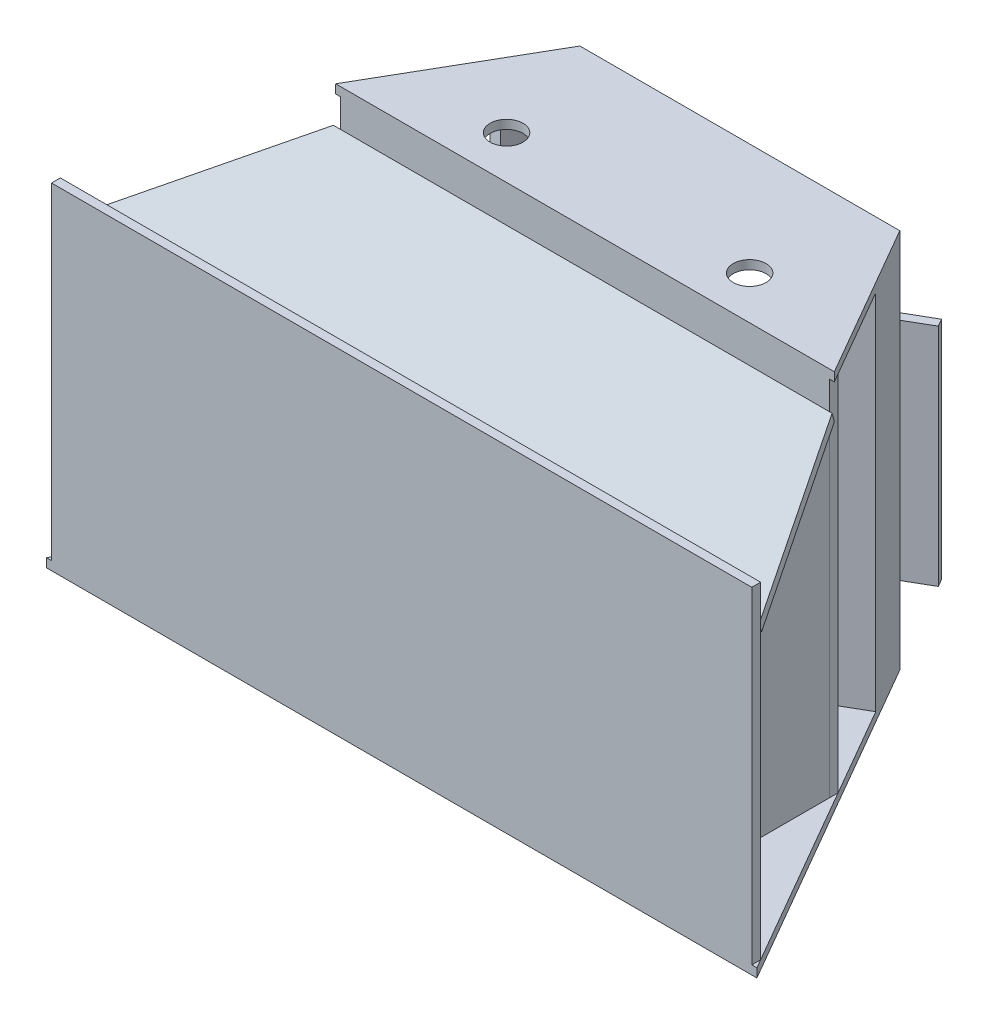
SolidWorks part; units mm, degrees
material "Pine"
ref_plane "Front Plane" through (0, 0, 0) normal (0, 0, 1) x (1, 0, 0)
ref_plane "Top Plane" through (0, 0, 0) normal (0, 1, 0) x (1, 0, 0)
ref_plane "Right Plane" through (0, 0, 0) normal (1, 0, 0) x (0, 0, -1)
sketch "TOP LAYOUT" plane through (0, 0, 0) normal (0, 1, 0) x (1, 0, 0)
  line L0 (-480.2035, -831.7368) -> (0, 0) construction
  line L1 (960.407, 0) -> (480.2035, 831.7368)
  line L2 (480.2035, 831.7368) -> (-480.2035, 831.7368)
  line L3 (-480.2035, 831.7368) -> (-960.407, 0)
  line L4 (-960.407, 0) -> (-480.2035, -831.7368)
  line L5 (-480.2035, -831.7368) -> (480.2035, -831.7368)
  line L6 (480.2035, -831.7368) -> (960.407, 0)
  line L7 (0, 0) -> (480.2035, -831.7368) construction
  circle A0 centre (0, 0) radius 831.7368 construction
  dimension "D1" = 1663.4737
sketch "REEF" plane through (0, 0, 0) normal (1, 0, 0) x (0, 0, -1)
  line L0 (-831.7368, 0) -> (-831.7368, 454.025)
  line L1 (-831.7368, 454.025) -> (-819.8306, 454.025)
  line L2 (-819.8306, 454.025) -> (-819.8306, 404.9259)
  line L3 (-819.8306, 404.9259) -> (-583.9002, 468.1433)
  line L4 (-583.9002, 468.1433) -> (-583.9002, 514.3505)
  line L5 (-583.9002, 514.3505) -> (-547.8322, 514.3505)
  line L6 (-547.8322, 514.3505) -> (-547.8322, 601.9982)
  line L7 (-547.8322, 601.9982) -> (-791.3462, 772.5085)
  line L8 (-791.3462, 772.5085) -> (-767.162, 807.0473)
  line L9 (-767.162, 807.0473) -> (-547.8322, 653.4709)
  line L10 (-547.8322, 653.4709) -> (-547.8322, 1005.0979)
  line L11 (-547.8322, 1005.0979) -> (-791.3462, 1175.6083)
  line L12 (-791.3462, 1175.6083) -> (-767.162, 1210.147)
  line L13 (-767.162, 1210.147) -> (-547.8322, 1056.5707)
  line L14 (-547.8322, 1056.5707) -> (-547.8322, 1366.2827)
  line L15 (-582.167, 1432.2392) -> (-749.5177, 1549.4194)
  line L16 (-801.8322, 1649.9146) -> (-801.8322, 1825.4878)
  line L17 (-801.8322, 1825.4878) -> (-759.6682, 1825.4878)
  line L18 (-759.6682, 1825.4878) -> (-759.6682, 1649.9146)
  line L19 (-725.3334, 1583.9581) -> (-557.9827, 1466.7779)
  line L20 (-505.6682, 1366.2827) -> (-505.6682, 0)
  line L21 (-505.6682, 0) -> (-831.7368, 0)
  line L23 (-819.8306, 404.9259) -> (-816.749, 393.4254)
  line L24 (-816.749, 393.4254) -> (-583.9002, 455.817)
  line L25 (-583.9002, 455.817) -> (-586.9818, 467.3176)
  arc A0 (-547.8322, 1366.2827) -> (-582.167, 1432.2392) centre (-628.3502, 1366.2827) ccw
  arc A1 (-759.6682, 1649.9146) -> (-725.3334, 1583.9581) centre (-679.1502, 1649.9146) ccw
  arc A2 (-557.9827, 1466.7779) -> (-505.6682, 1366.2827) centre (-628.3502, 1366.2827) cw
  arc A3 (-749.5177, 1549.4194) -> (-801.8322, 1649.9146) centre (-679.1502, 1649.9146) cw
  circle A4 centre (-679.7375, 906.8587) radius 203.2 construction
  circle A5 centre (-679.7375, 1309.9584) radius 203.2 construction
  point P22 (-815.9418, 405.9679)
  point P23 (-779.2541, 1192.8777)
  point P25 (-780.7502, 1825.4878)
  point P26 (-779.2541, 789.7779)
  dimension "D15" = 80.518
  dimension "D18" = 122.682
  dimension "D28" = 406.4
  dimension "D1" = 454.025
  dimension "D2" = 11.9062
  dimension "D3" = 42.164
  dimension "D4" = 42.164
  dimension "D5" = 42.164
  dimension "D7" = 42.164
  dimension "D8" = 42.164
  dimension "D9" = 15
  dimension "D10" = 48.0571
  dimension "D13" = 283.9047
  dimension "D14" = 514.3505
  dimension "D6" = 125
  dimension "D16" = 254
  dimension "D17" = 175.5732
  dimension "D19" = 1825.4878
  dimension "D20" = 789.7779
  dimension "D21" = 52.4827
  dimension "D22" = 1192.8777
  dimension "D23" = 145
  dimension "D24" = 906.8587
  dimension "D25" = 151.9993
  dimension "D26" = 403.0998
  dimension "D27" = 403.0998
  dimension "D29" = 11.9062
  dimension "D12" = 247.8367
  dimension "D11" = 15.7951
sketch "Sketch2" plane through (0, 0, 0) normal (0, 1, 0) x (1, 0, 0)
  line L0 (-480.2035, -831.7368) -> (-216.2389, -374.5368)
  line L1 (-216.2389, -374.5368) -> (216.2389, -374.5368)
  line L2 (216.2389, -374.5368) -> (480.2035, -831.7368)
  line L3 (480.2035, -831.7368) -> (-480.2035, -831.7368)
  line L4 (-480.2035, -831.7368) -> (480.2035, -831.7368) construction
  line L5 (-480.2035, -831.7368) -> (0, 0) construction
  line L6 (0, 0) -> (480.2035, -831.7368) construction
  dimension "D1" = 457.2
extrude "Boss-Extrude1" add sketch "Sketch2" along normal blind 11.9062
sketch "Sketch3" plane through (0, 11.9062, 0) normal (0, 1, 0) x (1, 0, 0)
  line L0 (-216.2389, -374.5368) -> (-480.2035, -831.7368) construction
  line L1 (-473.3294, -819.8306) -> (473.3294, -819.8306)
  line L2 (-473.3294, -819.8306) -> (-473.3294, -831.7368)
  line L3 (-473.3294, -831.7368) -> (473.3294, -831.7368)
  line L4 (473.3294, -819.8306) -> (473.3294, -831.7368)
  line L5 (-480.2035, -831.7368) -> (480.2035, -831.7368) construction
  line L6 (480.2035, -831.7368) -> (216.2389, -374.5368) construction
  dimension "D1" = 11.9062
extrude "Boss-Extrude2" add sketch "Sketch3" along normal up to vertex (442.1187 mm away) up to point (0, 454.025, 831.7368)
sketch "Sketch4" plane through (0, 11.9062, 0) normal (0, 1, 0) x (1, 0, 0)
  line L0 (-216.2389, -374.5368) -> (-473.3294, -819.8306) construction
  line L1 (-330.2409, -571.9939) -> (330.2409, -571.9939)
  line L2 (-330.2409, -571.9939) -> (-330.2409, -583.9002)
  line L3 (-330.2409, -583.9002) -> (330.2409, -583.9002)
  line L4 (330.2409, -571.9939) -> (330.2409, -583.9002)
  line L5 (473.3294, -819.8306) -> (216.2389, -374.5368) construction
  dimension "D1" = 11.9062
extrude "Boss-Extrude3" add sketch "Sketch4" along normal up to vertex (502.4442 mm away) up to point (0, 514.3505, 583.9002)
sketch "Sketch5" plane through (0, 514.3505, 0) normal (0, 1, 0) x (1, 0, 0)
  line L0 (-337.1149, -583.9002) -> (-216.2389, -374.5368)
  line L1 (-216.2389, -374.5368) -> (216.2389, -374.5368)
  line L2 (216.2389, -374.5368) -> (337.1149, -583.9002)
  line L3 (337.1149, -583.9002) -> (-337.1149, -583.9002)
  line L4 (-216.2389, -374.5368) -> (-330.2409, -571.9939) construction
  line L5 (216.2389, -374.5368) -> (-216.2389, -374.5368) construction
  line L6 (330.2409, -571.9939) -> (216.2389, -374.5368) construction
  line L7 (-330.2409, -583.9002) -> (330.2409, -583.9002) construction
extrude "Boss-Extrude4" add sketch "Sketch5" against normal blind 11.9062
sketch "Sketch6" plane through (0, 514.3505, 0) normal (0, 1, 0) x (1, 0, 0)
  line L0 (-164.3095, -525.6072) -> (164.3095, -525.6072) construction
  line L1 (-164.3095, -547.8322) -> (164.3095, -547.8322) construction
  circle A0 centre (-164.3095, -525.6072) radius 22.225
  circle A1 centre (164.3095, -525.6072) radius 22.225
  point P6 (0, -525.6072)
  dimension "D2" = 44.45
  dimension "D1" = 328.619
extrude "Cut-Extrude2" cut sketch "Sketch6" against normal up to next
ref_axis "Axis1" through (0, 455.817, 583.9002) along (1, 0, 0)
ref_plane "Plane1" through (0, 571.2581, 153.0682) normal (0, 0.9659, 0.2588) x (1, 0, 0)
ref_axis "Axis2" through (477.7909, 390.5291, 827.558) along (-0.4871, 0.226, -0.8436)
sketch "Sketch7" plane through (0, 571.2581, 153.0682) normal (0, 0.9659, 0.2588) x (1, 0, 0)
  line L0 (-471.5503, -687.093) -> (-337.1149, -446.0301)
  line L1 (-337.1149, -446.0301) -> (337.1149, -446.0301)
  line L2 (337.1149, -446.0301) -> (471.5503, -687.093)
  line L3 (471.5503, -687.093) -> (-471.5503, -687.093)
  line L4 (477.7909, -698.2833) -> (330.4161, -434.0181) construction
extrude "Boss-Extrude5" add sketch "Sketch7" along normal blind 11.9062 separate body
sketch "Sketch8" plane through (330.2409, 0, 0) normal (1, 0, 0) x (0, 0, -1)
  line L0 (-819.8306, 11.9062) -> (-819.8306, 392.5997)
  line L1 (-819.8306, 392.5997) -> (-583.9002, 455.817)
  line L2 (-583.9002, 455.817) -> (-583.9002, 11.9063)
  line L3 (-583.9002, 11.9063) -> (-819.8306, 11.9062)
  line L4 (-583.9002, 502.4442) -> (-583.9002, 11.9062) construction
  line L5 (-816.749, 393.4254) -> (-583.9002, 455.817) construction
  line L6 (-819.8306, 454.025) -> (-819.8306, 11.9062) construction
  line L7 (-819.8306, 11.9062) -> (-571.9939, 11.9062) construction
extrude "Boss-Extrude8" add sketch "Sketch8" against normal blind 11.9062 separate body
mirror "Mirror2" about plane through (0, 0, 0) normal (1, 0, 0) of bodies 108
sketch "Sketch9" plane through (0, 11.9062, 0) normal (0, 1, 0) x (1, 0, 0)
  line L0 (330.2409, -571.9939) -> (-330.2409, -571.9939) construction
  line L1 (-228.6, -571.9939) -> (228.6, -571.9939)
  line L2 (-228.6, -571.9939) -> (-228.6, -483.0939)
  line L3 (-228.6, -483.0939) -> (228.6, -483.0939)
  line L4 (228.6, -571.9939) -> (228.6, -483.0939)
  line L5 (0, -483.0939) -> (0, -374.5368) construction
  line L6 (216.2389, -374.5368) -> (-216.2389, -374.5368) construction
  dimension "D1" = 88.9
  dimension "D2" = 457.2
extrude "Boss-Extrude9" add sketch "Sketch9" along normal blind 2.921
sketch "Sketch10" plane through (0, 14.8272, 0) normal (0, 1, 0) x (1, 0, 0)
  line L4 (-228.6, -483.0939) -> (-228.6, -571.9939)
  line L5 (-228.6, -571.9939) -> (228.6, -571.9939)
  line L6 (228.6, -571.9939) -> (228.6, -483.0939)
  line L7 (228.6, -483.0939) -> (-228.6, -483.0939)
  line L8 (-228.6, -483.0939) -> (-228.6, -571.9939)
  line L9 (-228.6, -571.9939) -> (228.6, -571.9939)
  line L10 (228.6, -571.9939) -> (228.6, -483.0939)
  line L11 (228.6, -483.0939) -> (-228.6, -483.0939)
  circle A0 centre (-164.3095, -525.6072) radius 22.225 construction
  circle A1 centre (164.3095, -525.6072) radius 22.225 construction
  circle A2 centre (-164.3095, -525.6072) radius 22.225
  circle A3 centre (164.3095, -525.6072) radius 22.225
  dimension "D1" = 0
extrude "Boss-Extrude10" add sketch "Sketch10" along normal blind 88.9
hole_wizard "5/16 (0.3125) Diameter Hole1" positions "Sketch14" profile "Sketch15" hole size "5/16" standard "ANSI Inch"
sketch "Sketch14" plane through (0, 0, 483.0939) normal (0, 0, -1) x (-1, 0, 0)
  line L0 (186.5345, 103.7272) -> (142.0845, 103.7272) construction
  line L1 (-142.0845, 103.7272) -> (-186.5345, 103.7272) construction
  line L2 (186.5345, 103.7272) -> (142.0845, 103.7272)
  line L3 (-142.0845, 103.7272) -> (-186.5345, 103.7272)
  line L4 (-164.3095, 103.7272) -> (-164.3095, 78.3272)
  line L6 (164.3095, 103.7272) -> (164.3095, 78.3273)
  point P0 (-164.3095, 78.3272)
  point P2 (164.3095, 78.3273)
  dimension "D1" = 25.4
sketch "Sketch15" plane through (164.3095, 78.3272, 483.0939) normal (1, 0, 0) x (0, 1, 0)
  line L0 (0, 0) -> (0, 103.1909)
  line L1 (0, 103.1909) -> (3.9687, 100.8062)
  line L2 (3.9687, 100.8062) -> (3.9687, 0)
  line L5 (3.9687, 0) -> (0, 0)
  line L10 (0, 103.1909) -> (-3.9688, 100.8062) construction
  line L11 (0, -6.35) -> (0, 107.95) construction
  dimension "Hole Dia." = 7.9375
  dimension "Hole Depth" = 100.8062
  dimension "Drill Angle" = 118
sketch "Sketch11" plane through (0, 11.9062, 0) normal (0, 1, 0) x (1, 0, 0)
  line L0 (216.2389, -374.5368) -> (260.6889, -451.5265)
  line L1 (216.2389, -374.5368) -> (183.2434, -393.5868)
  line L2 (260.6889, -451.5265) -> (227.6934, -470.5765)
  line L3 (183.2434, -393.5868) -> (227.6934, -470.5765)
  line L4 (330.2409, -571.9939) -> (216.2389, -374.5368) construction
  line L5 (-216.2389, -374.5368) -> (-260.6889, -451.5265)
  line L6 (-216.2389, -374.5368) -> (-183.2434, -393.5868)
  line L7 (-260.6889, -451.5265) -> (-227.6934, -470.5765)
  line L8 (-183.2434, -393.5868) -> (-227.6934, -470.5765)
  line L9 (-216.2389, -374.5368) -> (-330.2409, -571.9939) construction
  dimension "D1" = 88.9
  dimension "D2" = 38.1
extrude "Boss-Extrude11" add sketch "Sketch11" along normal up to surface (490.538 mm away) up to face at (-164.3095, 502.4442, 503.3822)
sketch "Sketch12" plane through (216.2389, 0, 374.5368) normal (-0.5, 0, -0.866) x (-0.866, 0, 0.5)
  line L0 (38.1, 502.4442) -> (38.1, 11.9062) construction
  line L1 (38.1, 409.5752) -> (-38.1, 409.5752)
  line L2 (38.1, 409.5752) -> (38.1, 104.7752)
  line L3 (38.1, 104.7752) -> (-38.1, 104.7752)
  line L4 (-38.1, 409.5752) -> (-38.1, 104.7752)
  line L5 (0, 257.1752) -> (-38.1, 257.1752) construction
  line L6 (0, 502.4442) -> (0, 11.9062) construction
  dimension "D1" = 304.8
  dimension "D2" = 76.2
extrude "Boss-Extrude12" add sketch "Sketch12" along normal blind 11.9062
ref_axis "Axis3" through (0, -25.7175, 0) along (0, 1, 0)
sketch "Sketch18" plane through (318.3346, 0, 0) normal (1, 0, 0) x (0, 0, -1)
  line L0 (-816.749, 393.4254) -> (-583.9002, 455.817) construction
  line L1 (-622.0002, 445.6082) -> (-583.9002, 445.6082)
  line L2 (-622.0002, 445.6082) -> (-622.0002, 356.7082)
  line L3 (-622.0002, 356.7082) -> (-583.9002, 356.7082)
  line L4 (-583.9002, 445.6082) -> (-583.9002, 356.7082)
  line L5 (-583.9002, 502.4442) -> (-583.9002, 11.9062) construction
  line L6 (-819.8306, 454.025) -> (-819.8306, 11.9062) construction
  line L7 (-819.8306, 393.4254) -> (-781.7306, 393.4254)
  line L8 (-819.8306, 393.4254) -> (-819.8306, 304.5254)
  line L9 (-819.8306, 304.5254) -> (-781.7306, 304.5254)
  line L10 (-781.7306, 393.4254) -> (-781.7306, 304.5254)
  line L12 (-819.8306, 11.9062) -> (-781.7306, 11.9062)
  line L13 (-819.8306, 11.9062) -> (-819.8306, 100.8062)
  line L14 (-819.8306, 100.8062) -> (-781.7306, 100.8062)
  line L15 (-781.7306, 11.9062) -> (-781.7306, 100.8062)
  dimension "D1" = 88.9
  dimension "D2" = 38.1
  dimension "D3" = 88.9
  dimension "D4" = 38.1
  dimension "D5" = 88.9
  dimension "D6" = 38.1
extrude "Boss-Extrude15" add sketch "Sketch18" against normal up to surface (636.6692 mm away) separate body up to face at (-318.3346, 218.0573, 701.8654)
equation "\"D4@REEF\" = \"D3@REEF\""
equation "\"D5@REEF\" = \"D3@REEF\""
equation "\"D7@REEF\" = \"D3@REEF\""
equation "\"D8@REEF\" = \"D3@REEF\""
equation "\"D15@REEF\" = 4in -  ( 1.66in / 2 ) "
equation "\"Thick\"= 0.46875in"
equation "\"D1@Boss-Extrude1\"=\"Thick\""
equation "\"D1@Sketch3\"=\"Thick\""
equation "\"D1@Sketch4\"=\"Thick\""
equation "\"D1@Boss-Extrude4\"=\"Thick\""
equation "\"D29@REEF\"=\"Thick\""
equation "\"D1@Boss-Extrude5\"=\"Thick\""
equation "\"D1@Boss-Extrude8\" = \"Thick\""
equation "\"D2@REEF\"=\"Thick\""
equation "\"D1@Boss-Extrude12\"=\"Thick\""
